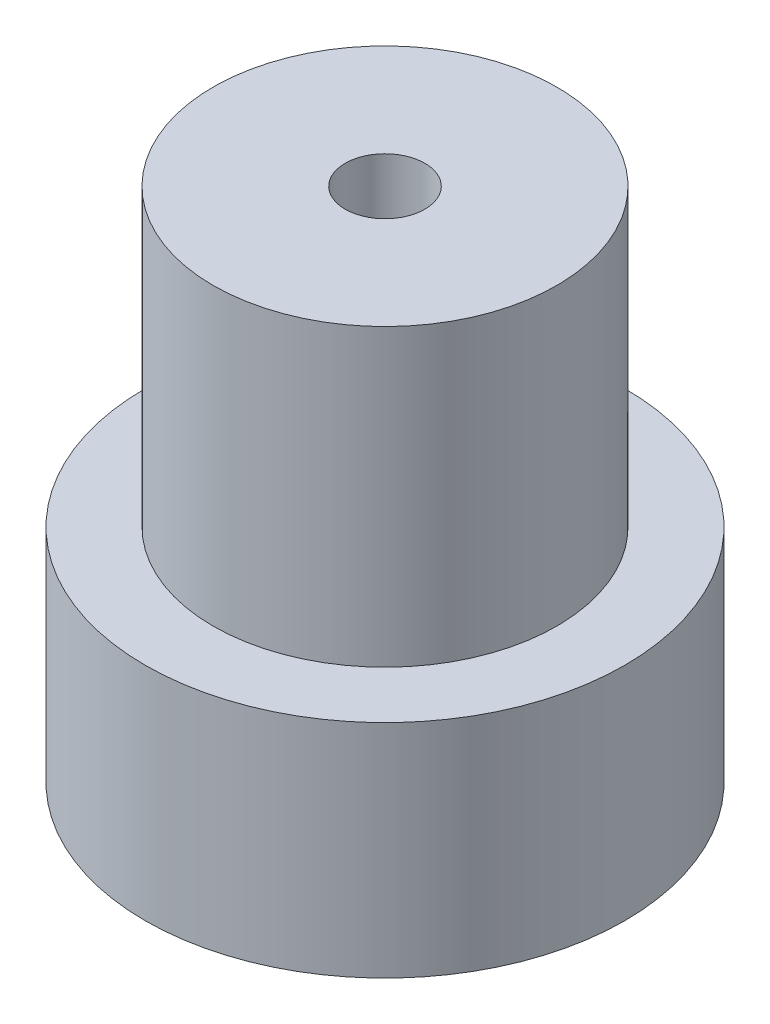
SolidWorks part; units mm, degrees
ref_plane "Front Plane" through (0, 0, 0) normal (0, 0, 1) x (1, 0, 0)
ref_plane "Top Plane" through (0, 0, 0) normal (0, 1, 0) x (1, 0, 0)
ref_plane "Right Plane" through (0, 0, 0) normal (1, 0, 0) x (0, 0, -1)
sketch "Sketch1" plane through (0, 0, 0) normal (0, 1, 0) x (1, 0, 0)
  circle A0 centre (0, 0) radius 16.25
  dimension "D1" = 32.5
extrude "Boss-Extrude1" add sketch "Sketch1" along normal blind 15
sketch "Sketch2" plane through (0, 15, 0) normal (0, 1, 0) x (1, 0, 0)
  circle A0 centre (0, 0) radius 11.65
  dimension "D1" = 23.3
extrude "Boss-Extrude2" add sketch "Sketch2" along normal blind 20
sketch "Sketch4" plane through (0, 35, 0) normal (0, 1, 0) x (1, 0, 0)
  circle A0 centre (0, 0) radius 2.7
extrude "Cut-Extrude1" cut sketch "Sketch4" against normal blind 30
